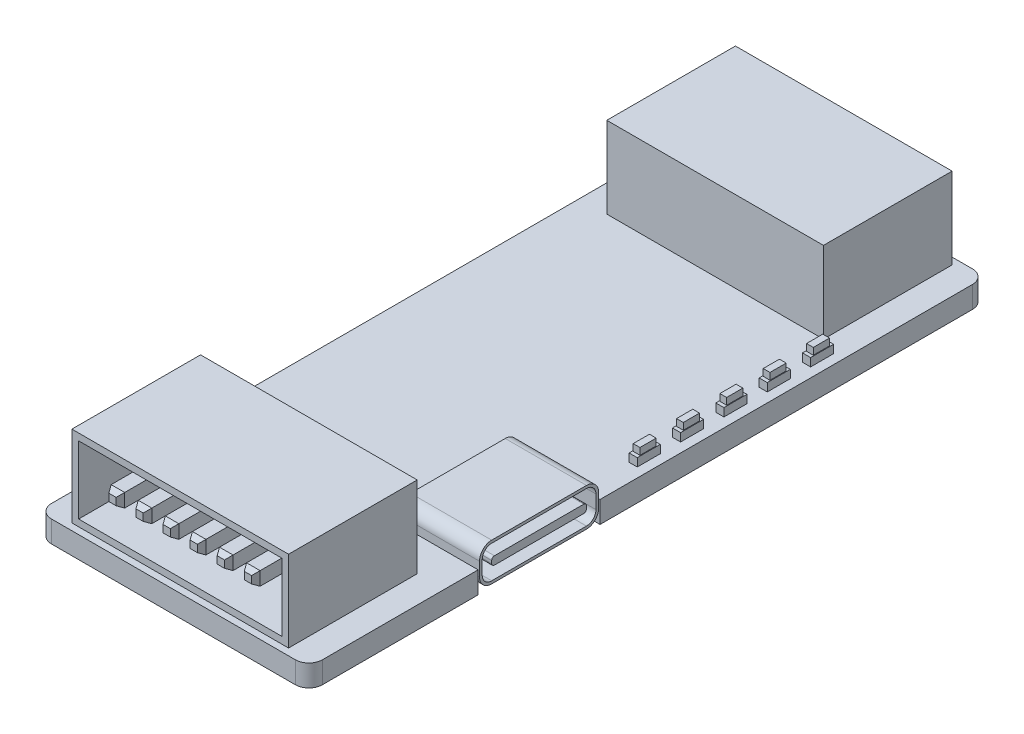
SolidWorks part; units mm, degrees
material "1023 碳钢板 (SS)"
ref_plane "前视基准面" through (0, 0, 0) normal (0, 0, 1) x (1, 0, 0)
ref_plane "上视基准面" through (0, 0, 0) normal (0, 1, 0) x (1, 0, 0)
ref_plane "右视基准面" through (0, 0, 0) normal (1, 0, 0) x (0, 0, -1)
sketch "草图1" plane through (0, 0, 0) normal (0, 1, 0) x (1, 0, 0)
  line L1 (-9, 25) -> (9, 25)
  line L2 (-10, 24) -> (-10, -24)
  line L3 (-9, -25) -> (9, -25)
  line L8 (10, -12.5) -> (4, -12.5)
  line L9 (4, -12.5) -> (4, -3.5)
  line L10 (4, -3.5) -> (10, -3.5)
  line L11 (10, 24) -> (10, -3.5)
  line L12 (10, -12.5) -> (10, -24)
  arc A0 (9, -25) -> (10, -24) centre (9, -24) ccw
  arc A1 (-9, -25) -> (-10, -24) centre (-9, -24) cw
  arc A2 (10, 24) -> (9, 25) centre (9, 24) ccw
  arc A3 (-10, 24) -> (-9, 25) centre (-9, 24) cw
  point P0 (0, 0)
  dimension "D1" = 1
extrude "凸台-拉伸1" add sketch "草图1" along normal blind 1.6
sketch "草图2" plane through (0, 1.6, 0) normal (0, 1, 0) x (1, 0, 0)
  line L3 (-8, 25) -> (8, 25)
  line L4 (-8, 25) -> (-8, 15)
  line L5 (-8, 15) -> (8, 15)
  line L6 (8, 25) -> (8, 15)
  line L7 (-8, 25) -> (8, 15) construction
  line L8 (-8, 15) -> (8, 25) construction
  line L11 (-8, -15) -> (8, -15)
  line L12 (-8, -15) -> (-8, -25)
  line L13 (-8, -25) -> (8, -25)
  line L14 (8, -15) -> (8, -25)
  line L15 (-8, -15) -> (8, -25) construction
  line L16 (-8, -25) -> (8, -15) construction
extrude "凸台-拉伸2" add sketch "草图2" along normal blind 6
sketch "草图3" plane through (4, 0, 0) normal (1, 0, 0) x (0, 0, -1)
  line L0 (-12.5, 1.6) -> (-3.5, 1.6) construction
  line L1 (-3.5, 3.1) -> (-12.5, 3.1)
  line L2 (-3.5, 3.1) -> (-3.5, 0.1)
  line L3 (-3.5, 0.1) -> (-12.5, 0.1)
  line L4 (-12.5, 3.1) -> (-12.5, 0.1)
  line L5 (-3.5, 3.1) -> (-12.5, 0.1) construction
  line L6 (-3.5, 0.1) -> (-12.5, 3.1) construction
  point P0 (-8, 1.6)
extrude "凸台-拉伸3" add sketch "草图3" along normal blind 6
sketch "草图4" plane through (10, 0, 0) normal (1, 0, 0) x (0, 0, -1)
  line L0 (-12.5, 0.1) -> (-3.5, 0.1) construction
  line L2 (-12.5, 3.1) -> (-12.5, 1.6) construction
  line L4 (-3.5, 1.1) -> (-3.5, 0.1)
  line L6 (-12.5, 1.1) -> (-12.5, 0.1)
  line L7 (-3.5, 3.1) -> (-12.5, 3.1) construction
  line L8 (-3.5, 1.6) -> (-3.5, 3.1) construction
  line L9 (-12.5, 0.1) -> (-11.5, 0.1)
  line L10 (-12.5, 3.1) -> (-12.5, 2.1)
  line L11 (-3.5, 3.1) -> (-4.5, 3.1)
  line L12 (-3.5, 2.1) -> (-3.5, 3.1)
  line L13 (-4.5, 0.1) -> (-3.5, 0.1)
  line L14 (-11.5, 3.1) -> (-12.5, 3.1)
  arc A0 (-12.5, 1.1) -> (-11.5, 0.1) centre (-11.5, 1.1) ccw
  arc A1 (-12.5, 2.1) -> (-11.5, 3.1) centre (-11.5, 2.1) cw
  arc A2 (-4.5, 0.1) -> (-3.5, 1.1) centre (-4.5, 1.1) ccw
  arc A3 (-4.5, 3.1) -> (-3.5, 2.1) centre (-4.5, 2.1) cw
  dimension "D1" = 1
extrude "切除-拉伸1" cut sketch "草图4" against normal blind 6
sketch "草图5" plane through (10, 0, 0) normal (1, 0, 0) x (0, 0, -1)
  line L0 (-11.5, 0.1) -> (-4.5, 0.1) construction
  line L1 (-12.5, 2.1) -> (-12.5, 1.6) construction
  line L2 (-4.5, 3.1) -> (-11.5, 3.1) construction
  line L3 (-3.5, 1.6) -> (-3.5, 2.1) construction
  line L4 (-11.5, 0.1) -> (-4.5, 0.1)
  line L5 (-12.5, 2.1) -> (-12.5, 1.1)
  line L6 (-4.5, 3.1) -> (-11.5, 3.1)
  line L7 (-3.5, 1.1) -> (-3.5, 2.1)
  line L8 (-11.5, 0.2) -> (-4.5, 0.2)
  line L9 (-3.6, 1.1) -> (-3.6, 2.1)
  line L10 (-4.5, 3) -> (-11.5, 3)
  line L11 (-12.4, 2.1) -> (-12.4, 1.1)
  arc A0 (-4.5, 0.1) -> (-3.5, 1.1) centre (-4.5, 1.1) ccw construction
  arc A1 (-12.5, 1.1) -> (-11.5, 0.1) centre (-11.5, 1.1) ccw construction
  arc A2 (-11.5, 3.1) -> (-12.5, 2.1) centre (-11.5, 2.1) ccw construction
  arc A3 (-3.5, 2.1) -> (-4.5, 3.1) centre (-4.5, 2.1) ccw construction
  arc A4 (-4.5, 0.1) -> (-3.5, 1.1) centre (-4.5, 1.1) ccw
  arc A5 (-12.5, 1.1) -> (-11.5, 0.1) centre (-11.5, 1.1) ccw
  arc A6 (-11.5, 3.1) -> (-12.5, 2.1) centre (-11.5, 2.1) ccw
  arc A7 (-3.5, 2.1) -> (-4.5, 3.1) centre (-4.5, 2.1) ccw
  arc A8 (-4.5, 0.2) -> (-3.6, 1.1) centre (-4.5, 1.1) ccw
  arc A9 (-3.6, 2.1) -> (-4.5, 3) centre (-4.5, 2.1) ccw
  arc A10 (-11.5, 3) -> (-12.4, 2.1) centre (-11.5, 2.1) ccw
  arc A11 (-12.4, 1.1) -> (-11.5, 0.2) centre (-11.5, 1.1) ccw
  dimension "D1" = 0.1
extrude "切除-拉伸2" cut sketch "草图5" against normal blind 6
sketch "草图6" plane through (10, 0, 0) normal (1, 0, 0) x (0, 0, -1)
  line L0 (-11.5, 0.4) -> (-4.5, 0.4)
  line L1 (-3.8, 1.1) -> (-3.8, 2.1)
  line L2 (-4.5, 2.8) -> (-11.5, 2.8)
  line L3 (-12.2, 2.1) -> (-12.2, 1.1)
  line L6 (-4.7, 1.9) -> (-11.3, 1.9)
  line L7 (-4.5, 1.7) -> (-4.5, 1.5)
  line L8 (-4.7, 1.3) -> (-11.3, 1.3)
  line L9 (-11.5, 1.7) -> (-11.5, 1.5)
  arc A0 (-4.5, 0.4) -> (-3.8, 1.1) centre (-4.5, 1.1) ccw
  arc A1 (-3.8, 2.1) -> (-4.5, 2.8) centre (-4.5, 2.1) ccw
  arc A2 (-11.5, 2.8) -> (-12.2, 2.1) centre (-11.5, 2.1) ccw
  arc A3 (-12.2, 1.1) -> (-11.5, 0.4) centre (-11.5, 1.1) ccw
  arc A4 (-11.5, 1.5) -> (-11.3, 1.3) centre (-11.3, 1.5) ccw
  arc A5 (-11.5, 1.7) -> (-11.3, 1.9) centre (-11.3, 1.7) cw
  arc A6 (-4.7, 1.3) -> (-4.5, 1.5) centre (-4.7, 1.5) ccw
  arc A7 (-4.7, 1.9) -> (-4.5, 1.7) centre (-4.7, 1.7) cw
  point P3 (-8, 1.6)
  dimension "D1" = 0.2
extrude "切除-拉伸4" cut sketch "草图6" against normal blind 5
sketch "草图7" plane through (0, 0, -25) normal (0, 0, -1) x (-1, 0, 0)
  line L3 (8, 1.6) -> (-8, 1.6)
  line L4 (8, 1.6) -> (8, 7.6)
  line L5 (8, 7.6) -> (-8, 7.6)
  line L6 (-8, 1.6) -> (-8, 7.6)
  line L7 (8, 1.6) -> (-8, 7.6) construction
  line L8 (8, 7.6) -> (-8, 1.6) construction
extrude "切除-拉伸5" cut sketch "草图7" against normal blind 0.5
sketch "草图8" plane through (0, 0, 25) normal (0, 0, 1) x (1, 0, 0)
  line L3 (8, 1.6) -> (-8, 1.6)
  line L4 (8, 1.6) -> (8, 7.6)
  line L5 (8, 7.6) -> (-8, 7.6)
  line L6 (-8, 1.6) -> (-8, 7.6)
  line L7 (8, 1.6) -> (-8, 7.6) construction
  line L8 (8, 7.6) -> (-8, 1.6) construction
extrude "切除-拉伸6" cut sketch "草图8" against normal blind 0.5
sketch "草图9" plane through (0, 1.6, 0) normal (0, 1, 0) x (1, 0, 0)
  line L3 (8.7, 14.45) -> (9.3, 14.45)
  line L4 (8.7, 14.45) -> (8.7, 12.75)
  line L5 (8.7, 12.75) -> (9.3, 12.75)
  line L6 (9.3, 14.45) -> (9.3, 12.75)
  line L7 (8.7, 14.45) -> (9.3, 12.75) construction
  line L8 (8.7, 12.75) -> (9.3, 14.45) construction
extrude "凸台-拉伸4" add sketch "草图9" along normal blind 0.6
sketch "草图10" plane through (0, 2.2, 0) normal (0, 1, 0) x (1, 0, 0)
  line L4 (8.75, 14.2) -> (9.25, 14.2)
  line L5 (8.75, 14.2) -> (8.75, 13)
  line L6 (8.75, 13) -> (9.25, 13)
  line L7 (9.25, 14.2) -> (9.25, 13)
  line L8 (8.75, 14.2) -> (9.25, 13) construction
  line L9 (8.75, 13) -> (9.25, 14.2) construction
  point P6 (9, 13.6)
extrude "凸台-拉伸6" add sketch "草图10" along normal blind 0.5
pattern_linear "阵列(线性)1" count 5 spacing 3.2 along (0, 0, 1) of "凸台-拉伸4", "凸台-拉伸6"
sketch "草图11" plane through (0, 0, 0) normal (0, -1, 0) x (-1, 0, 0)
  line L2 (-2.6, 17.6) -> (2.6, 17.6)
  line L3 (-2.6, 17.6) -> (-2.6, 12.4)
  line L4 (-2.6, 12.4) -> (2.6, 12.4)
  line L5 (2.6, 17.6) -> (2.6, 12.4)
  line L6 (-2.6, 17.6) -> (2.6, 12.4) construction
  line L7 (-2.6, 12.4) -> (2.6, 17.6) construction
extrude "凸台-拉伸7" add sketch "草图11" along normal blind 1.3
sketch "草图12" plane through (0, -1.3, 0) normal (0, -1, 0) x (-1, 0, 0)
  circle A0 centre (0, 15) radius 1
extrude "凸台-拉伸8" add sketch "草图12" along normal blind 0.2
chamfer "倒角1" distance 1 angle 45 4 edges at (2.6, -0.65, -17.6) (-2.6, -0.65, -17.6) (-2.6, -0.65, -12.4) (2.6, -0.65, -12.4)
sketch "草图13" plane through (0, -1.3, 0) normal (0, -1, 0) x (-1, 0, 0)
  line L0 (1.1858, 16.6) -> (-1.1858, 16.6)
  line L1 (-1.1858, 16.6) -> (-1.6, 16.1858)
  line L2 (-1.6, 16.1858) -> (-1.6, 13.8142)
  line L3 (-1.6, 13.8142) -> (-1.1858, 13.4)
  line L4 (-1.1858, 13.4) -> (1.1858, 13.4)
  line L5 (1.1858, 13.4) -> (1.6, 13.8142)
  line L6 (1.6, 13.8142) -> (1.6, 16.1858)
  line L7 (1.6, 16.1858) -> (1.1858, 16.6)
  line L8 (1.6, 17.6) -> (-1.6, 17.6)
  line L9 (-1.6, 17.6) -> (-2.6, 16.6)
  line L10 (-2.6, 16.6) -> (-2.6, 13.4)
  line L11 (-2.6, 13.4) -> (-1.6, 12.4)
  line L12 (-1.6, 12.4) -> (1.6, 12.4)
  line L13 (1.6, 12.4) -> (2.6, 13.4)
  line L14 (2.6, 13.4) -> (2.6, 16.6)
  line L15 (2.6, 16.6) -> (1.6, 17.6)
  line L16 (1.6, 17.6) -> (-1.6, 17.6)
  line L17 (-1.6, 17.6) -> (-2.6, 16.6)
  line L18 (-2.6, 16.6) -> (-2.6, 13.4)
  line L19 (-2.6, 13.4) -> (-1.6, 12.4)
  line L20 (-1.6, 12.4) -> (1.6, 12.4)
  line L21 (1.6, 12.4) -> (2.6, 13.4)
  line L22 (2.6, 13.4) -> (2.6, 16.6)
  line L23 (2.6, 16.6) -> (1.6, 17.6)
  dimension "D1" = 0
  dimension "D2" = 1
extrude "切除-拉伸7" cut sketch "草图13" against normal blind 0.5
fillet "圆角1" radius 0.5 16 edges at (1.6, -0.4, -17.6) (2.6, -0.4, -16.6) (-1.6, -0.4, -17.6) (-2.6, -0.4, -16.6) (-2.6, -0.4, -13.4) (-1.6, -0.4, -12.4) (1.6, -0.4, -12.4) (2.6, -0.4, -13.4) (1.6, -1.05, -13.8142) (1.1858, -1.05, -13.4) (-1.1858, -1.05, -13.4) (-1.6, -1.05, -13.8142) (-1.6, -1.05, -16.1858) (-1.1858, -1.05, -16.6) (1.1858, -1.05, -16.6) (1.6, -1.05, -16.1858)
fillet "圆角2" radius 0.25 48 edges at (2.5619, -0.8, -16.5842) (2.1, -0.8, -17.1) (1.5842, -0.8, -17.5619) (0, -0.8, -17.6) (-1.5842, -0.8, -17.5619) (-2.1, -0.8, -17.1) (-2.5619, -0.8, -16.5842) (-2.6, -0.8, -15) (-2.5619, -0.8, -13.4158) (-2.1, -0.8, -12.9) (-1.5842, -0.8, -12.4381) (0, -0.8, -12.4) (1.5842, -0.8, -12.4381) (2.1, -0.8, -12.9) (2.5619, -0.8, -13.4158) (1.5619, -1.3, -16.17) (1.3929, -1.3, -16.3929) (1.17, -1.3, -16.5619) (0, -1.3, -16.6) (-1.17, -1.3, -16.5619) (-1.3929, -1.3, -16.3929) (-1.5619, -1.3, -16.17) (-1.6, -1.3, -15) (-1.5619, -1.3, -13.83) (-1.3929, -1.3, -13.6071) (-1.17, -1.3, -13.4381) (0, -1.3, -13.4) (1.17, -1.3, -13.4381) (1.3929, -1.3, -13.6071) (1.5619, -1.3, -13.83) (1.5619, -0.8, -16.17) (1.3929, -0.8, -16.3929) (1.17, -0.8, -16.5619) (0, -0.8, -16.6) (-1.17, -0.8, -16.5619) (-1.3929, -0.8, -16.3929) (-1.5619, -0.8, -16.17) (-1.6, -0.8, -15) (-1.5619, -0.8, -13.83) (-1.3929, -0.8, -13.6071) (-1.17, -0.8, -13.4381) (0, -0.8, -13.4) (1.17, -0.8, -13.4381) (1.3929, -0.8, -13.6071) (1.5619, -0.8, -13.83) (2.6, -0.8, -15) (1.6, -1.3, -15) (1.6, -0.8, -15)
fillet "圆角3" radius 0.1 1 edges at (0, -1.5, -16)
sketch "草图14" plane through (0, 0, -24.5) normal (0, 0, -1) x (-1, 0, 0)
  line L0 (-7.5, 7.1) -> (-7.5, 2.1)
  line L1 (-7.5, 2.1) -> (7.5, 2.1)
  line L2 (7.5, 2.1) -> (7.5, 7.1)
  line L3 (7.5, 7.1) -> (-7.5, 7.1)
  line L4 (-8, 7.6) -> (-8, 1.6)
  line L5 (-8, 1.6) -> (8, 1.6)
  line L6 (8, 1.6) -> (8, 7.6)
  line L7 (8, 7.6) -> (-8, 7.6)
  line L8 (-8, 7.6) -> (-8, 1.6)
  line L9 (-8, 1.6) -> (8, 1.6)
  line L10 (8, 1.6) -> (8, 7.6)
  line L11 (8, 7.6) -> (-8, 7.6)
  line L12 (2.5, 5.1) -> (2.5, 4.1)
  line L13 (2.5, 5.1) -> (3.5, 5.1)
  line L14 (3.5, 5.1) -> (3.5, 4.1)
  line L15 (4.5, 5.1) -> (5.5, 5.1)
  line L16 (4.5, 5.1) -> (4.5, 4.1)
  line L17 (4.5, 4.1) -> (5.5, 4.1)
  line L18 (5.5, 5.1) -> (5.5, 4.1)
  line L19 (4.5, 5.1) -> (5.5, 4.1) construction
  line L20 (4.5, 4.1) -> (5.5, 5.1) construction
  line L21 (2.5, 4.1) -> (3.5, 4.1)
  line L22 (0.5, 5.1) -> (0.5, 4.1)
  line L23 (0.5, 5.1) -> (1.5, 5.1)
  line L24 (1.5, 5.1) -> (1.5, 4.1)
  line L25 (0.5, 4.1) -> (1.5, 4.1)
  line L26 (-1.5, 5.1) -> (-1.5, 4.1)
  line L27 (-1.5, 5.1) -> (-0.5, 5.1)
  line L28 (-0.5, 5.1) -> (-0.5, 4.1)
  line L29 (-1.5, 4.1) -> (-0.5, 4.1)
  line L30 (-3.5, 5.1) -> (-3.5, 4.1)
  line L31 (-3.5, 5.1) -> (-2.5, 5.1)
  line L32 (-2.5, 5.1) -> (-2.5, 4.1)
  line L33 (-3.5, 4.1) -> (-2.5, 4.1)
  line L34 (-5.5, 5.1) -> (-5.5, 4.1)
  line L35 (-5.5, 5.1) -> (-4.5, 5.1)
  line L36 (-4.5, 5.1) -> (-4.5, 4.1)
  line L37 (-5.5, 4.1) -> (-4.5, 4.1)
  dimension "D3" = 6
  dimension "D1" = 0
  dimension "D2" = 0.5
extrude "切除-拉伸8" cut sketch "草图14" against normal blind 8 contours L2 L3 L0 L1 L37 L34 L35 L36 L33 L30 L31 L32 L29 L26 L27 L28 L25 L22 L23 L24 L21 L12 L13 L14 L15 L18 L17 L16 region at (0, 4.6, -24.5)
chamfer "倒角3" distance 0.4 angle 30 4 edges at (-4.5, 4.6, -24.5) (-5, 4.1, -24.5) (-5.5, 4.6, -24.5) (-5, 5.1, -24.5) first distance on face at (-4.5, 4.6, -20.5) first distance on face at (-5, 4.1, -20.5) first distance on face at (-5.5, 4.6, -20.5) first distance on face at (-5, 5.1, -20.5)
chamfer "倒角4" distance 0.4 angle 30 20 edges at (-3, 5.1, -24.5) (-3.5, 4.6, -24.5) (-3, 4.1, -24.5) (-2.5, 4.6, -24.5) (-1, 5.1, -24.5) (-1.5, 4.6, -24.5) (-1, 4.1, -24.5) (-0.5, 4.6, -24.5) (1, 5.1, -24.5) (0.5, 4.6, -24.5) (1, 4.1, -24.5) (1.5, 4.6, -24.5) (3, 5.1, -24.5) (2.5, 4.6, -24.5) (3, 4.1, -24.5) (3.5, 4.6, -24.5) (5, 5.1, -24.5) (4.5, 4.6, -24.5) (5, 4.1, -24.5) (5.5, 4.6, -24.5) first distance on face at (-3, 5.1, -20.5) first distance on face at (-3.5, 4.6, -20.5) first distance on face at (-3, 4.1, -20.5) first distance on face at (-2.5, 4.6, -20.5) first distance on face at (-1, 5.1, -20.5) first distance on face at (-1.5, 4.6, -20.5) first distance on face at (-1, 4.1, -20.5) first distance on face at (-0.5, 4.6, -20.5) first distance on face at (1, 5.1, -20.5) first distance on face at (0.5, 4.6, -20.5) first distance on face at (1, 4.1, -20.5) first distance on face at (1.5, 4.6, -20.5) first distance on face at (3, 5.1, -20.5) first distance on face at (2.5, 4.6, -20.5) first distance on face at (3, 4.1, -20.5) first distance on face at (3.5, 4.6, -20.5) first distance on face at (5, 5.1, -20.5) first distance on face at (4.5, 4.6, -20.5) first distance on face at (5, 4.1, -20.5) first distance on face at (5.5, 4.6, -20.5)
mirror "镜向3" about plane through (0, 0, 0) normal (0, 0, 1) of "切除-拉伸8"
chamfer "倒角5" distance 0.4 angle 30 24 edges at (4.5, 4.6, 24.5) (5, 5.1, 24.5) (5.5, 4.6, 24.5) (5, 4.1, 24.5) (2.5, 4.6, 24.5) (3, 5.1, 24.5) (3.5, 4.6, 24.5) (3, 4.1, 24.5) (0.5, 4.6, 24.5) (1, 5.1, 24.5) (1.5, 4.6, 24.5) (1, 4.1, 24.5) (-1.5, 4.6, 24.5) (-1, 5.1, 24.5) (-0.5, 4.6, 24.5) (-1, 4.1, 24.5) (-3.5, 4.6, 24.5) (-3, 5.1, 24.5) (-2.5, 4.6, 24.5) (-3, 4.1, 24.5) (-5, 4.1, 24.5) (-5.5, 4.6, 24.5) (-5, 5.1, 24.5) (-4.5, 4.6, 24.5) first distance on face at (4.5, 4.6, 20.5) first distance on face at (5, 5.1, 20.5) first distance on face at (5.5, 4.6, 20.5) first distance on face at (5, 4.1, 20.5) first distance on face at (2.5, 4.6, 20.5) first distance on face at (3, 5.1, 20.5) first distance on face at (3.5, 4.6, 20.5) first distance on face at (3, 4.1, 20.5) first distance on face at (0.5, 4.6, 20.5) first distance on face at (1, 5.1, 20.5) first distance on face at (1.5, 4.6, 20.5) first distance on face at (1, 4.1, 20.5) first distance on face at (-1.5, 4.6, 20.5) first distance on face at (-1, 5.1, 20.5) first distance on face at (-0.5, 4.6, 20.5) first distance on face at (-1, 4.1, 20.5) first distance on face at (-3.5, 4.6, 20.5) first distance on face at (-3, 5.1, 20.5) first distance on face at (-2.5, 4.6, 20.5) first distance on face at (-3, 4.1, 20.5) first distance on face at (-5, 4.1, 20.5) first distance on face at (-5.5, 4.6, 20.5) first distance on face at (-5, 5.1, 20.5) first distance on face at (-4.5, 4.6, 20.5)
